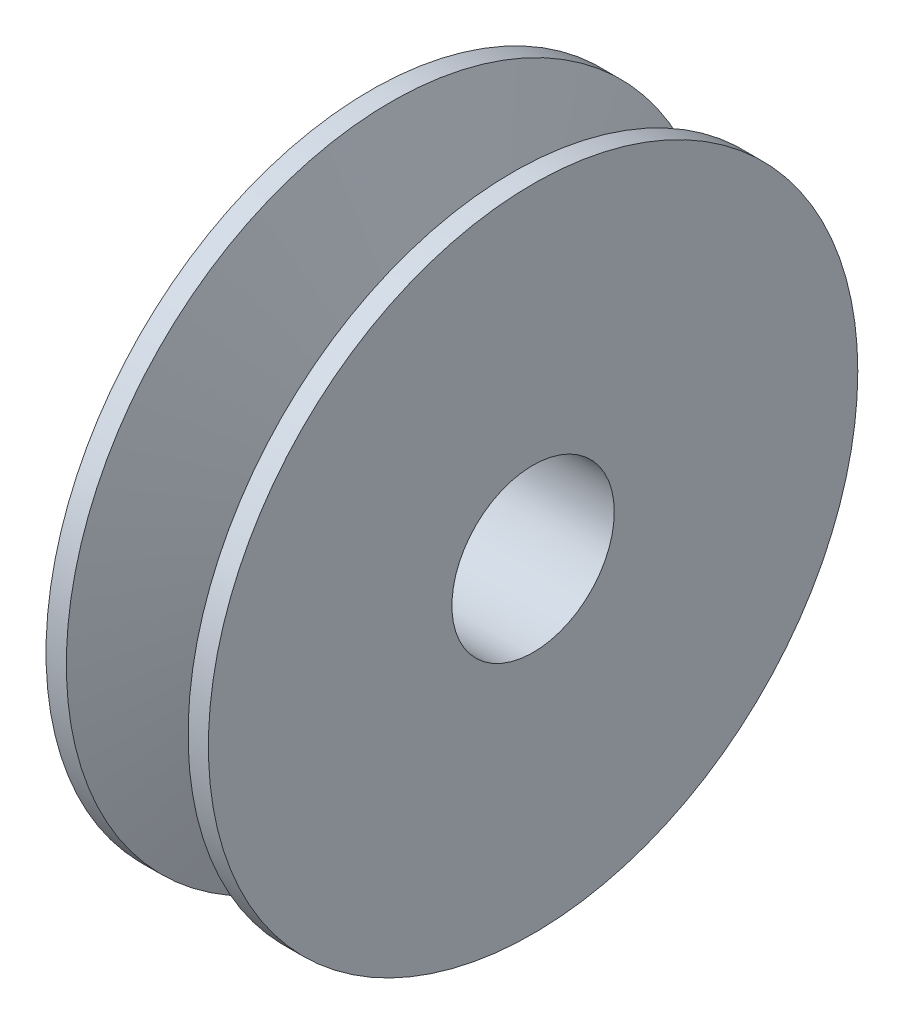
SolidWorks part; units mm, degrees
ref_plane "Front Plane" through (0, 0, 0) normal (0, 0, 1) x (1, 0, 0)
ref_plane "Top Plane" through (0, 0, 0) normal (0, 1, 0) x (1, 0, 0)
ref_plane "Right Plane" through (0, 0, 0) normal (1, 0, 0) x (0, 0, -1)
sketch "Sketch1" plane through (0, 0, 0) normal (0, 0, 1) x (1, 0, 0)
  line L0 (0, 0) -> (-68.2529, 0) construction
  line L1 (0, 12.7) -> (0, 50.8)
  line L2 (0, 50.8) -> (-3.175, 50.8)
  line L3 (-3.175, 50.8) -> (-8.9992, 31.75)
  line L4 (-8.9992, 31.75) -> (-16.4008, 31.75)
  line L5 (-16.4008, 31.75) -> (-22.225, 50.8)
  line L6 (-22.225, 50.8) -> (-25.4, 50.8)
  line L7 (-25.4, 50.8) -> (-25.4, 12.7)
  line L8 (-25.4, 12.7) -> (0, 12.7)
  dimension "D1" = 34
  dimension "D2" = 19.05
  dimension "D3" = 50.8
  dimension "D4" = 25.4
  dimension "D5" = 19.05
  dimension "D6" = 3.175
revolve "Revolve1" add sketch "Sketch1" angle 360 about L0
